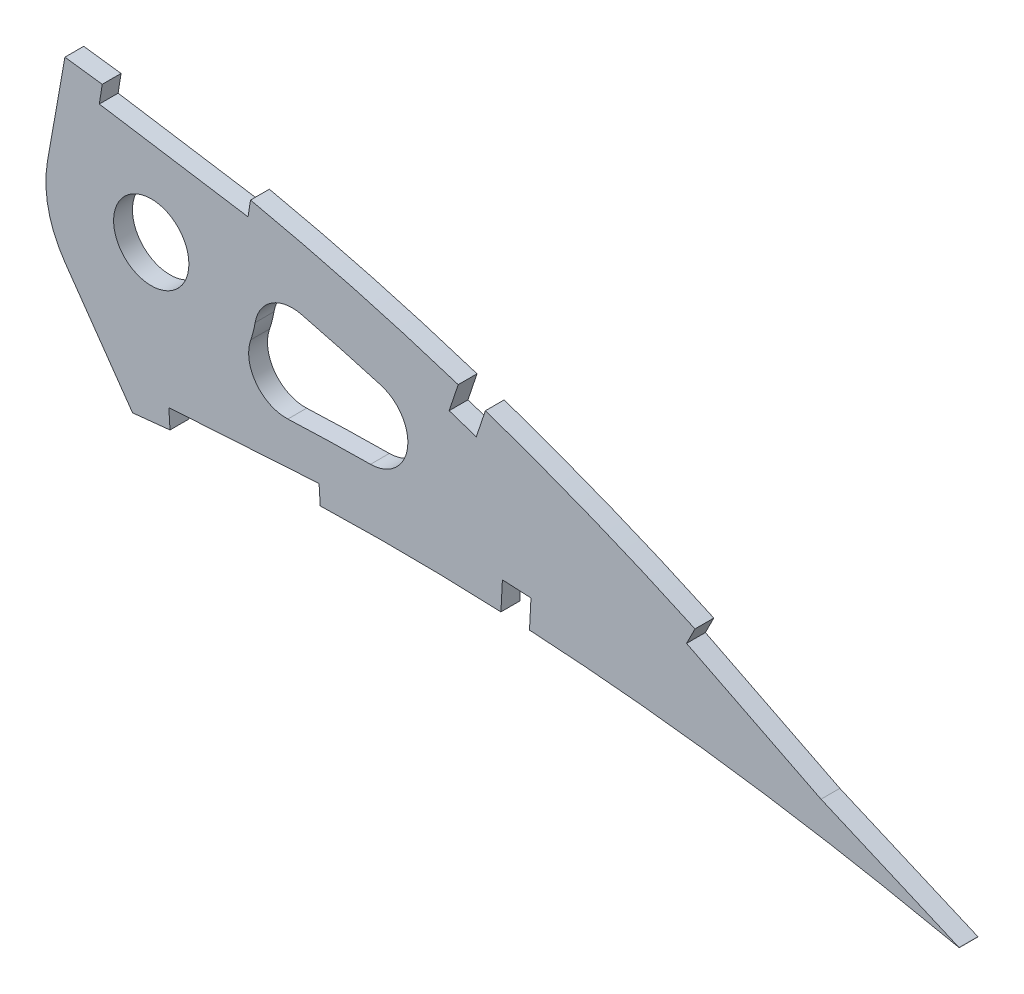
SolidWorks part; units mm, degrees
material "Plywood"
ref_plane "Front Plane" through (0, 0, 0) normal (0, 0, 1) x (1, 0, 0)
ref_plane "Top Plane" through (0, 0, 0) normal (0, 1, 0) x (1, 0, 0)
ref_plane "Right Plane" through (0, 0, 0) normal (1, 0, 0) x (0, 0, -1)
curve "Curve1"
  spline degree 3 poles (0, 0, 0) (0.1249, -0.5894, 0) (0.3751, -1.7709, 0) (1.0551, -3.4717, 0) (1.9543, -5.1067, 0) (3.0917, -6.6716, 0) (4.4597, -8.1658, 0) (6.0551, -9.5909, 0) (7.8766, -10.9463, 0) (9.9217, -12.2312, 0) (12.1874, -13.447, 0) (14.6712, -14.593, 0) (17.3708, -15.6688, 0) (20.2833, -16.6729, 0) (23.4051, -17.607, 0) (26.7332, -18.4687, 0) (30.2639, -19.2592, 0) (33.9938, -19.9766, 0) (37.9188, -20.6214, 0) (42.0348, -21.1935, 0) (46.3376, -21.6931, 0) (50.823, -22.1192, 0) (55.4866, -22.4726, 0) (60.3236, -22.7538, 0) (65.3294, -22.9634, 0) (70.4993, -23.1008, 0) (75.828, -23.1681, 0) (81.3109, -23.1662, 0) (86.9426, -23.0948, 0) (92.7182, -22.9577, 0) (98.6323, -22.754, 0) (104.6794, -22.4863, 0) (110.8541, -22.1572, 0) (117.1509, -21.7679, 0) (123.5642, -21.32, 0) (130.0885, -20.8172, 0) (136.7178, -20.2607, 0) (143.4464, -19.6538, 0) (150.2683, -18.9994, 0) (157.1776, -18.2998, 0) (164.1682, -17.5581, 0) (171.2339, -16.7767, 0) (178.3687, -15.9599, 0) (185.566, -15.1091, 0) (192.8198, -14.2292, 0) (200.1233, -13.3218, 0) (207.4703, -12.3905, 0) (214.8542, -11.4396, 0) (222.2681, -10.469, 0) (229.7058, -9.4856, 0) (237.1601, -8.4887, 0) (244.6246, -7.4833, 0) (252.0922, -6.4726, 0) (259.5558, -5.4569, 0) (267.0088, -4.4404, 0) (274.4442, -3.4259, 0) (281.8548, -2.4135, 0) (289.2339, -1.4081, 0) (296.574, -0.4098, 0) (303.8684, 0.5795, 0) (311.1101, 1.5569, 0) (318.2922, 2.521, 0) (325.4074, 3.4714, 0) (332.4485, 4.4082, 0) (339.3029, 5.3032, 0) (345.9529, 6.204, 0) (352.4207, 6.9424, 0) (358.808, 7.5727, 0) (365.1214, 8.0894, 0) (371.3533, 8.5001, 0) (377.4966, 8.8075, 0) (383.544, 9.0161, 0) (389.4878, 9.132, 0) (395.3205, 9.1582, 0) (401.0343, 9.1029, 0) (406.6218, 8.9708, 0) (412.075, 8.7675, 0) (417.3864, 8.5002, 0) (422.5485, 8.1759, 0) (427.5535, 7.7996, 0) (432.3944, 7.38, 0) (437.0637, 6.9232, 0) (441.5544, 6.4344, 0) (445.8598, 5.924, 0) (449.973, 5.3952, 0) (453.8879, 4.8568, 0) (457.5982, 4.3142, 0) (461.0979, 3.7743, 0) (464.3817, 3.2423, 0) (467.4441, 2.7253, 0) (470.2803, 2.228, 0) (472.8856, 1.7553, 0) (475.2562, 1.3133, 0) (477.3874, 0.904, 0) (479.2765, 0.5343, 0) (480.9199, 0.2058, 0) (482.3151, -0.077, 0) (483.4599, -0.3128, 0) (484.3523, -0.4979, 0) (484.9907, -0.6325, 0) (485.3743, -0.7125, 0) (485.5448, -0.7489, 0) (485.5874, -0.758, 0) knots 0 0 0 0 0.003638 0.007293 0.011028 0.014901 0.018963 0.023258 0.027821 0.032679 0.037853 0.043362 0.049215 0.055422 0.061989 0.068918 0.076211 0.083868 0.091887 0.100266 0.109 0.118085 0.127515 0.137285 0.147388 0.157816 0.168563 0.179619 0.190977 0.202627 0.21456 0.226767 0.239236 0.251959 0.264924 0.27812 0.291536 0.30516 0.318981 0.332985 0.347163 0.361499 0.375981 0.390597 0.405333 0.420175 0.43511 0.450124 0.465203 0.480333 0.495501 0.51069 0.525887 0.541078 0.556247 0.571382 0.586466 0.601485 0.616424 0.631269 0.646007 0.660621 0.675098 0.689423 0.703582 0.716908 0.730009 0.742952 0.755726 0.76832 0.780724 0.792927 0.804916 0.816679 0.828204 0.839475 0.850481 0.861208 0.871639 0.881763 0.891564 0.901027 0.910139 0.918884 0.927249 0.935221 0.942785 0.949928 0.956638 0.962904 0.968712 0.974054 0.978918 0.983297 0.98718 0.990561 0.993433 0.995791 0.99763 0.998946 0.999737 1 1 1 1
curve "Curve2"
  spline degree 3 poles (486.1938, 0.758, 0) (486.1565, 0.781, 0) (486.0077, 0.8729, 0) (485.6723, 1.0786, 0) (485.1139, 1.4213, 0) (484.3321, 1.8984, 0) (483.3276, 2.5088, 0) (482.0999, 3.2482, 0) (480.6498, 4.1141, 0) (478.9775, 5.1026, 0) (477.0833, 6.2089, 0) (474.9678, 7.4286, 0) (472.6313, 8.7548, 0) (470.0748, 10.182, 0) (467.2989, 11.7035, 0) (464.3043, 13.3123, 0) (461.0921, 15.0004, 0) (457.6635, 16.7605, 0) (454.019, 18.5827, 0) (450.1605, 20.4596, 0) (446.0892, 22.3819, 0) (441.8065, 24.3391, 0) (437.3149, 26.3234, 0) (432.6155, 28.3224, 0) (427.7112, 30.3274, 0) (422.6039, 32.3272, 0) (417.2967, 34.3124, 0) (411.7916, 36.2703, 0) (406.0928, 38.1924, 0) (400.203, 40.0661, 0) (394.1264, 41.8812, 0) (387.8666, 43.626, 0) (381.4288, 45.2916, 0) (374.8171, 46.8658, 0) (368.037, 48.3381, 0) (361.0939, 49.6996, 0) (353.9938, 50.9366, 0) (346.7562, 52.0484, 0) (339.4976, 52.9732, 0) (332.2539, 53.8802, 0) (325.021, 54.7322, 0) (317.6998, 55.5482, 0) (310.2971, 56.3235, 0) (302.8205, 57.0556, 0) (295.2774, 57.7415, 0) (287.6757, 58.3791, 0) (280.0227, 58.9648, 0) (272.3266, 59.4977, 0) (264.5949, 59.9731, 0) (256.8359, 60.3907, 0) (249.0573, 60.7475, 0) (241.2675, 61.0411, 0) (233.4745, 61.2698, 0) (225.6865, 61.4312, 0) (217.912, 61.5245, 0) (210.159, 61.547, 0) (202.4359, 61.4984, 0) (194.7508, 61.377, 0) (187.1122, 61.1811, 0) (179.5282, 60.9103, 0) (172.0069, 60.5649, 0) (164.5567, 60.1418, 0) (157.1855, 59.6438, 0) (149.9016, 59.0688, 0) (142.713, 58.4167, 0) (135.6273, 57.6901, 0) (128.6522, 56.887, 0) (121.7954, 56.0099, 0) (115.0642, 55.0603, 0) (108.4663, 54.0378, 0) (102.0087, 52.9453, 0) (95.6983, 51.784, 0) (89.542, 50.5572, 0) (83.5463, 49.2652, 0) (77.7176, 47.912, 0) (72.062, 46.4999, 0) (66.5855, 45.0315, 0) (61.2937, 43.5103, 0) (56.192, 41.9397, 0) (51.2862, 40.3215, 0) (46.5802, 38.6618, 0) (42.0796, 36.9619, 0) (37.788, 35.2268, 0) (33.7103, 33.4591, 0) (29.8497, 31.6641, 0) (26.2104, 29.8437, 0) (22.7951, 28.0033, 0) (19.6072, 26.1454, 0) (16.6497, 24.2737, 0) (13.924, 22.3929, 0) (11.4337, 20.504, 0) (9.1798, 18.612, 0) (7.1636, 16.7197, 0) (5.388, 14.8284, 0) (3.8531, 12.9414, 0) (2.5606, 11.0602, 0) (1.511, 9.1866, 0) (0.7066, 7.3219, 0) (0.1466, 5.4673, 0) (-0.16, 3.6254, 0) (-0.2363, 1.7948, 0) (-0.0786, 0.5974, 0) (0, 0, 0) knots 0 0 0 0 0.000254 0.001015 0.002283 0.004057 0.006331 0.009105 0.012374 0.016134 0.02038 0.025106 0.030306 0.035972 0.0421 0.048678 0.055702 0.06316 0.071046 0.07935 0.088063 0.097176 0.106678 0.116562 0.126814 0.137428 0.148394 0.1597 0.171338 0.183298 0.19557 0.208144 0.221012 0.234162 0.247587 0.261277 0.275223 0.289414 0.303771 0.317689 0.331784 0.34604 0.360444 0.374983 0.38964 0.404403 0.419257 0.434187 0.449177 0.464215 0.479284 0.49437 0.509458 0.524532 0.539579 0.554583 0.56953 0.584403 0.599191 0.613877 0.628447 0.642889 0.657186 0.671326 0.685294 0.699078 0.712665 0.726043 0.739198 0.752118 0.764792 0.777208 0.789356 0.801224 0.812804 0.824083 0.835055 0.84571 0.856038 0.866034 0.875689 0.884998 0.893953 0.902553 0.910789 0.918661 0.926166 0.933303 0.940071 0.946475 0.952518 0.958205 0.963547 0.968557 0.97325 0.977651 0.981787 0.985694 0.989415 0.993001 0.996508 1 1 1 1
sketch "Sketch1" plane through (0, 0, 0) normal (0, 0, 1) x (1, 0, 0)
  line L10 (485.5874, -0.758) -> (490.1477, -1.6846)
  line L24 (486.1938, 0.758) -> (490.1477, -1.6846)
  spline S2 degree 3 poles (-3866.8103, -1018.8258) (79.7559, 75.3438) (-9.1933, 22.1629) (1.0551, -3.4717) (1.9543, -5.1067) (3.0917, -6.6716) (4.4597, -8.1658) (6.0551, -9.5909) (7.8766, -10.9463) (9.9217, -12.2312) (12.1874, -13.447) (14.6712, -14.593) (17.3708, -15.6688) (20.2833, -16.6729) (23.4051, -17.607) (26.7332, -18.4687) (30.2639, -19.2592) (33.9938, -19.9766) (37.9188, -20.6214) (42.0348, -21.1935) (46.3376, -21.6931) (50.823, -22.1192) (55.4866, -22.4726) (60.3236, -22.7538) (65.3294, -22.9634) (70.4993, -23.1008) (75.828, -23.1681) (81.3109, -23.1662) (86.9426, -23.0948) (92.7182, -22.9577) (98.6323, -22.754) (104.6794, -22.4863) (110.8541, -22.1572) (117.1509, -21.7679) (123.5642, -21.32) (130.0885, -20.8172) (136.7178, -20.2607) (143.4464, -19.6538) (150.2683, -18.9994) (157.1776, -18.2998) (164.1682, -17.5581) (171.2339, -16.7767) (178.3687, -15.9599) (185.566, -15.1091) (192.8198, -14.2292) (200.1233, -13.3218) (207.4703, -12.3905) (214.8542, -11.4396) (222.2681, -10.469) (229.7058, -9.4856) (237.1601, -8.4887) (244.6246, -7.4833) (252.0922, -6.4726) (259.5558, -5.4569) (267.0088, -4.4404) (274.4442, -3.4259) (281.8548, -2.4135) (289.2339, -1.4081) (296.574, -0.4098) (303.8684, 0.5795) (311.1101, 1.5569) (318.2922, 2.521) (325.4074, 3.4714) (332.4485, 4.4082) (339.3029, 5.3032) (345.9529, 6.204) (352.4207, 6.9424) (358.808, 7.5727) (365.1214, 8.0894) (371.3533, 8.5001) (377.4966, 8.8075) (383.544, 9.0161) (389.4878, 9.132) (395.3205, 9.1582) (401.0343, 9.1029) (406.6218, 8.9708) (412.075, 8.7675) (417.3864, 8.5002) (422.5485, 8.1759) (427.5535, 7.7996) (432.3944, 7.38) (437.0637, 6.9232) (441.5544, 6.4344) (445.8598, 5.924) (449.973, 5.3952) (453.8879, 4.8568) (457.5982, 4.3142) (461.0979, 3.7743) (464.3817, 3.2423) (467.4441, 2.7253) (470.2803, 2.228) (472.8856, 1.7553) (475.2562, 1.3133) (477.3874, 0.904) (479.2765, 0.5343) (480.9199, 0.2058) (482.3151, -0.077) (483.4599, -0.3128) (484.3523, -0.4979) (484.9907, -0.6325) (504.0158, -4.6034) (520.901, -17.6411) (1368.8084, 3899.3631) knots -0.155184 -0.155184 -0.155184 -0.155184 0.003638 0.007293 0.011028 0.014901 0.018963 0.023258 0.027821 0.032679 0.037853 0.043362 0.049215 0.055422 0.061989 0.068918 0.076211 0.083868 0.091887 0.100266 0.109 0.118085 0.127515 0.137285 0.147388 0.157816 0.168563 0.179619 0.190977 0.202627 0.21456 0.226767 0.239236 0.251959 0.264924 0.27812 0.291536 0.30516 0.318981 0.332985 0.347163 0.361499 0.375981 0.390597 0.405333 0.420175 0.43511 0.450124 0.465203 0.480333 0.495501 0.51069 0.525887 0.541078 0.556247 0.571382 0.586466 0.601485 0.616424 0.631269 0.646007 0.660621 0.675098 0.689423 0.703582 0.716908 0.730009 0.742952 0.755726 0.76832 0.780724 0.792927 0.804916 0.816679 0.828204 0.839475 0.850481 0.861208 0.871639 0.881763 0.891564 0.901027 0.910139 0.918884 0.927249 0.935221 0.942785 0.949928 0.956638 0.962904 0.968712 0.974054 0.978918 0.983297 0.98718 0.990561 0.993433 0.995791 0.99763 0.998946 0.999737 1.115177 1.115177 1.115177 1.115177 only from (0, 0) to (485.5874, -0.758) construction
  spline S3 degree 3 poles (2637.6242, 3371.1949) (518.0891, -28.6046) (504.1645, -10.2642) (485.6723, 1.0786) (485.1139, 1.4213) (484.3321, 1.8984) (483.3276, 2.5088) (482.0999, 3.2482) (480.6498, 4.1141) (478.9775, 5.1026) (477.0833, 6.2089) (474.9678, 7.4286) (472.6313, 8.7548) (470.0748, 10.182) (467.2989, 11.7035) (464.3043, 13.3123) (461.0921, 15.0004) (457.6635, 16.7605) (454.019, 18.5827) (450.1605, 20.4596) (446.0892, 22.3819) (441.8065, 24.3391) (437.3149, 26.3234) (432.6155, 28.3224) (427.7112, 30.3274) (422.6039, 32.3272) (417.2967, 34.3124) (411.7916, 36.2703) (406.0928, 38.1924) (400.203, 40.0661) (394.1264, 41.8812) (387.8666, 43.626) (381.4288, 45.2916) (374.8171, 46.8658) (368.037, 48.3381) (361.0939, 49.6996) (353.9938, 50.9366) (346.7562, 52.0484) (339.4976, 52.9732) (332.2539, 53.8802) (325.021, 54.7322) (317.6998, 55.5482) (310.2971, 56.3235) (302.8205, 57.0556) (295.2774, 57.7415) (287.6757, 58.3791) (280.0227, 58.9648) (272.3266, 59.4977) (264.5949, 59.9731) (256.8359, 60.3907) (249.0573, 60.7475) (241.2675, 61.0411) (233.4745, 61.2698) (225.6865, 61.4312) (217.912, 61.5245) (210.159, 61.547) (202.4359, 61.4984) (194.7508, 61.377) (187.1122, 61.1811) (179.5282, 60.9103) (172.0069, 60.5649) (164.5567, 60.1418) (157.1855, 59.6438) (149.9016, 59.0688) (142.713, 58.4167) (135.6273, 57.6901) (128.6522, 56.887) (121.7954, 56.0099) (115.0642, 55.0603) (108.4663, 54.0378) (102.0087, 52.9453) (95.6983, 51.784) (89.542, 50.5572) (83.5463, 49.2652) (77.7176, 47.912) (72.062, 46.4999) (66.5855, 45.0315) (61.2937, 43.5103) (56.192, 41.9397) (51.2862, 40.3215) (46.5802, 38.6618) (42.0796, 36.9619) (37.788, 35.2268) (33.7103, 33.4591) (29.8497, 31.6641) (26.2104, 29.8437) (22.7951, 28.0033) (19.6072, 26.1454) (16.6497, 24.2737) (13.924, 22.3929) (11.4337, 20.504) (9.1798, 18.612) (7.1636, 16.7197) (5.388, 14.8284) (3.8531, 12.9414) (2.5606, 11.0602) (1.511, 9.1866) (0.7066, 7.3219) (0.1466, 5.4673) (-0.16, 3.6254) (-1.3078, -23.9112) (100.477, -44.4073) (-3985.5392, -325.5751) knots -0.123624 -0.123624 -0.123624 -0.123624 0.000254 0.001015 0.002283 0.004057 0.006331 0.009105 0.012374 0.016134 0.02038 0.025106 0.030306 0.035972 0.0421 0.048678 0.055702 0.06316 0.071046 0.07935 0.088063 0.097176 0.106678 0.116562 0.126814 0.137428 0.148394 0.1597 0.171338 0.183298 0.19557 0.208144 0.221012 0.234162 0.247587 0.261277 0.275223 0.289414 0.303771 0.317689 0.331784 0.34604 0.360444 0.374983 0.38964 0.404403 0.419257 0.434187 0.449177 0.464215 0.479284 0.49437 0.509458 0.524532 0.539579 0.554583 0.56953 0.584403 0.599191 0.613877 0.628447 0.642889 0.657186 0.671326 0.685294 0.699078 0.712665 0.726043 0.739198 0.752118 0.764792 0.777208 0.789356 0.801224 0.812804 0.824083 0.835055 0.84571 0.856038 0.866034 0.875689 0.884998 0.893953 0.902553 0.910789 0.918661 0.926166 0.933303 0.940071 0.946475 0.952518 0.958205 0.963547 0.968557 0.97325 0.977651 0.981787 0.985694 0.989415 0.993001 0.996508 1.148636 1.148636 1.148636 1.148636 only from (486.1938, 0.758) to (0, 0) construction
  spline S4 degree 3 poles (0, 0) (0.1249, -0.5894) (0.3751, -1.7709) (1.0551, -3.4717) (1.9543, -5.1067) (3.0917, -6.6716) (4.4597, -8.1658) (6.0551, -9.5909) (7.8766, -10.9463) (9.9217, -12.2312) (12.1874, -13.447) (14.6712, -14.593) (17.3708, -15.6688) (20.2833, -16.6729) (23.4051, -17.607) (26.7332, -18.4687) (30.2639, -19.2592) (33.9938, -19.9766) (37.9188, -20.6214) (42.0348, -21.1935) (46.3376, -21.6931) (50.823, -22.1192) (55.4866, -22.4726) (60.3236, -22.7538) (65.3294, -22.9634) (70.4993, -23.1008) (75.828, -23.1681) (81.3109, -23.1662) (86.9426, -23.0948) (92.7182, -22.9577) (98.6323, -22.754) (104.6794, -22.4863) (110.8541, -22.1572) (117.1509, -21.7679) (123.5642, -21.32) (130.0885, -20.8172) (136.7178, -20.2607) (143.4464, -19.6538) (150.2683, -18.9994) (157.1776, -18.2998) (164.1682, -17.5581) (171.2339, -16.7767) (178.3687, -15.9599) (185.566, -15.1091) (192.8198, -14.2292) (200.1233, -13.3218) (207.4703, -12.3905) (214.8542, -11.4396) (222.2681, -10.469) (229.7058, -9.4856) (237.1601, -8.4887) (244.6246, -7.4833) (252.0922, -6.4726) (259.5558, -5.4569) (267.0088, -4.4404) (274.4442, -3.4259) (281.8548, -2.4135) (289.2339, -1.4081) (296.574, -0.4098) (303.8684, 0.5795) (311.1101, 1.5569) (318.2922, 2.521) (325.4074, 3.4714) (332.4485, 4.4082) (339.3029, 5.3032) (345.9529, 6.204) (352.4207, 6.9424) (358.808, 7.5727) (365.1214, 8.0894) (371.3533, 8.5001) (377.4966, 8.8075) (383.544, 9.0161) (389.4878, 9.132) (395.3205, 9.1582) (401.0343, 9.1029) (406.6218, 8.9708) (412.075, 8.7675) (417.3864, 8.5002) (422.5485, 8.1759) (427.5535, 7.7996) (432.3944, 7.38) (437.0637, 6.9232) (441.5544, 6.4344) (445.8598, 5.924) (449.973, 5.3952) (453.8879, 4.8568) (457.5982, 4.3142) (461.0979, 3.7743) (464.3817, 3.2423) (467.4441, 2.7253) (470.2803, 2.228) (472.8856, 1.7553) (475.2562, 1.3133) (477.3874, 0.904) (479.2765, 0.5343) (480.9199, 0.2058) (482.3151, -0.077) (483.4599, -0.3128) (484.3523, -0.4979) (484.9907, -0.6325) (485.3743, -0.7125) (485.5448, -0.7489) (485.5874, -0.758) knots 0 0 0 0 0.003638 0.007293 0.011028 0.014901 0.018963 0.023258 0.027821 0.032679 0.037853 0.043362 0.049215 0.055422 0.061989 0.068918 0.076211 0.083868 0.091887 0.100266 0.109 0.118085 0.127515 0.137285 0.147388 0.157816 0.168563 0.179619 0.190977 0.202627 0.21456 0.226767 0.239236 0.251959 0.264924 0.27812 0.291536 0.30516 0.318981 0.332985 0.347163 0.361499 0.375981 0.390597 0.405333 0.420175 0.43511 0.450124 0.465203 0.480333 0.495501 0.51069 0.525887 0.541078 0.556247 0.571382 0.586466 0.601485 0.616424 0.631269 0.646007 0.660621 0.675098 0.689423 0.703582 0.716908 0.730009 0.742952 0.755726 0.76832 0.780724 0.792927 0.804916 0.816679 0.828204 0.839475 0.850481 0.861208 0.871639 0.881763 0.891564 0.901027 0.910139 0.918884 0.927249 0.935221 0.942785 0.949928 0.956638 0.962904 0.968712 0.974054 0.978918 0.983297 0.98718 0.990561 0.993433 0.995791 0.99763 0.998946 0.999737 1 1 1 1
  spline S5 degree 3 poles (486.1938, 0.758) (486.1565, 0.781) (486.0077, 0.8729) (485.6723, 1.0786) (485.1139, 1.4213) (484.3321, 1.8984) (483.3276, 2.5088) (482.0999, 3.2482) (480.6498, 4.1141) (478.9775, 5.1026) (477.0833, 6.2089) (474.9678, 7.4286) (472.6313, 8.7548) (470.0748, 10.182) (467.2989, 11.7035) (464.3043, 13.3123) (461.0921, 15.0004) (457.6635, 16.7605) (454.019, 18.5827) (450.1605, 20.4596) (446.0892, 22.3819) (441.8065, 24.3391) (437.3149, 26.3234) (432.6155, 28.3224) (427.7112, 30.3274) (422.6039, 32.3272) (417.2967, 34.3124) (411.7916, 36.2703) (406.0928, 38.1924) (400.203, 40.0661) (394.1264, 41.8812) (387.8666, 43.626) (381.4288, 45.2916) (374.8171, 46.8658) (368.037, 48.3381) (361.0939, 49.6996) (353.9938, 50.9366) (346.7562, 52.0484) (339.4976, 52.9732) (332.2539, 53.8802) (325.021, 54.7322) (317.6998, 55.5482) (310.2971, 56.3235) (302.8205, 57.0556) (295.2774, 57.7415) (287.6757, 58.3791) (280.0227, 58.9648) (272.3266, 59.4977) (264.5949, 59.9731) (256.8359, 60.3907) (249.0573, 60.7475) (241.2675, 61.0411) (233.4745, 61.2698) (225.6865, 61.4312) (217.912, 61.5245) (210.159, 61.547) (202.4359, 61.4984) (194.7508, 61.377) (187.1122, 61.1811) (179.5282, 60.9103) (172.0069, 60.5649) (164.5567, 60.1418) (157.1855, 59.6438) (149.9016, 59.0688) (142.713, 58.4167) (135.6273, 57.6901) (128.6522, 56.887) (121.7954, 56.0099) (115.0642, 55.0603) (108.4663, 54.0378) (102.0087, 52.9453) (95.6983, 51.784) (89.542, 50.5572) (83.5463, 49.2652) (77.7176, 47.912) (72.062, 46.4999) (66.5855, 45.0315) (61.2937, 43.5103) (56.192, 41.9397) (51.2862, 40.3215) (46.5802, 38.6618) (42.0796, 36.9619) (37.788, 35.2268) (33.7103, 33.4591) (29.8497, 31.6641) (26.2104, 29.8437) (22.7951, 28.0033) (19.6072, 26.1454) (16.6497, 24.2737) (13.924, 22.3929) (11.4337, 20.504) (9.1798, 18.612) (7.1636, 16.7197) (5.388, 14.8284) (3.8531, 12.9414) (2.5606, 11.0602) (1.511, 9.1866) (0.7066, 7.3219) (0.1466, 5.4673) (-0.16, 3.6254) (-0.2363, 1.7948) (-0.0786, 0.5974) (0, 0) knots 0 0 0 0 0.000254 0.001015 0.002283 0.004057 0.006331 0.009105 0.012374 0.016134 0.02038 0.025106 0.030306 0.035972 0.0421 0.048678 0.055702 0.06316 0.071046 0.07935 0.088063 0.097176 0.106678 0.116562 0.126814 0.137428 0.148394 0.1597 0.171338 0.183298 0.19557 0.208144 0.221012 0.234162 0.247587 0.261277 0.275223 0.289414 0.303771 0.317689 0.331784 0.34604 0.360444 0.374983 0.38964 0.404403 0.419257 0.434187 0.449177 0.464215 0.479284 0.49437 0.509458 0.524532 0.539579 0.554583 0.56953 0.584403 0.599191 0.613877 0.628447 0.642889 0.657186 0.671326 0.685294 0.699078 0.712665 0.726043 0.739198 0.752118 0.764792 0.777208 0.789356 0.801224 0.812804 0.824083 0.835055 0.84571 0.856038 0.866034 0.875689 0.884998 0.893953 0.902553 0.910789 0.918661 0.926166 0.933303 0.940071 0.946475 0.952518 0.958205 0.963547 0.968557 0.97325 0.977651 0.981787 0.985694 0.989415 0.993001 0.996508 1 1 1 1
extrude "Boss-Extrude1" add sketch "Sketch1" along normal blind 3.175
sketch "Sketch5" plane through (0, 0, 3.175) normal (0, 0, 1) x (1, 0, 0)
  line L0 (336.323, 36.32) -> (339.2642, 53)
  line L1 (339.2684, 23.0344) -> (350.6801, 6.7368)
  line L2 (353.8329, 33.2326) -> (374.466, 33.2326)
  circle A0 centre (353.8329, 33.2326) radius 6.35
  circle A1 centre (353.8329, 33.2326) radius 6.35
  circle A2 centre (353.8329, 33.2326) radius 17.78
  spline S0 degree 3 poles (-1939.0794, -487.5307) (48.5631, 55.4905) (-7.2206, 17.2286) (1.0551, -3.4717) (1.9543, -5.1067) (3.0917, -6.6716) (4.4597, -8.1658) (6.0551, -9.5909) (7.8766, -10.9463) (9.9217, -12.2312) (12.1874, -13.447) (14.6712, -14.593) (17.3708, -15.6688) (20.2833, -16.6729) (23.4051, -17.607) (26.7332, -18.4687) (30.2639, -19.2592) (33.9938, -19.9766) (37.9188, -20.6214) (42.0348, -21.1935) (46.3376, -21.6931) (50.823, -22.1192) (55.4866, -22.4726) (60.3236, -22.7538) (65.3294, -22.9634) (70.4993, -23.1008) (75.828, -23.1681) (81.3109, -23.1662) (86.9426, -23.0948) (92.7182, -22.9577) (98.6323, -22.754) (104.6794, -22.4863) (110.8541, -22.1572) (117.1509, -21.7679) (123.5642, -21.32) (130.0885, -20.8172) (136.7178, -20.2607) (143.4464, -19.6538) (150.2683, -18.9994) (157.1776, -18.2998) (164.1682, -17.5581) (171.2339, -16.7767) (178.3687, -15.9599) (185.566, -15.1091) (192.8198, -14.2292) (200.1233, -13.3218) (207.4703, -12.3905) (214.8542, -11.4396) (222.2681, -10.469) (229.7058, -9.4856) (237.1601, -8.4887) (244.6246, -7.4833) (252.0922, -6.4726) (259.5558, -5.4569) (267.0088, -4.4404) (274.4442, -3.4259) (281.8548, -2.4135) (289.2339, -1.4081) (296.574, -0.4098) (303.8684, 0.5795) (311.1101, 1.5569) (318.2922, 2.521) (325.4074, 3.4714) (332.4485, 4.4082) (339.3029, 5.3032) (345.9529, 6.204) (352.4207, 6.9424) (358.808, 7.5727) (365.1214, 8.0894) (371.3533, 8.5001) (377.4966, 8.8075) (383.544, 9.0161) (389.4878, 9.132) (395.3205, 9.1582) (401.0343, 9.1029) (406.6218, 8.9708) (412.075, 8.7675) (417.3864, 8.5002) (422.5485, 8.1759) (427.5535, 7.7996) (432.3944, 7.38) (437.0637, 6.9232) (441.5544, 6.4344) (445.8598, 5.924) (449.973, 5.3952) (453.8879, 4.8568) (457.5982, 4.3142) (461.0979, 3.7743) (464.3817, 3.2423) (467.4441, 2.7253) (470.2803, 2.228) (472.8856, 1.7553) (475.2562, 1.3133) (477.3874, 0.904) (479.2765, 0.5343) (480.9199, 0.2058) (482.3151, -0.077) (483.4599, -0.3128) (484.3523, -0.4979) (484.9907, -0.6325) (500.1693, -3.8005) (513.9154, -12.6904) (943.5402, 1945.4943) knots -0.123191 -0.123191 -0.123191 -0.123191 0.003638 0.007293 0.011028 0.014901 0.018963 0.023258 0.027821 0.032679 0.037853 0.043362 0.049215 0.055422 0.061989 0.068918 0.076211 0.083868 0.091887 0.100266 0.109 0.118085 0.127515 0.137285 0.147388 0.157816 0.168563 0.179619 0.190977 0.202627 0.21456 0.226767 0.239236 0.251959 0.264924 0.27812 0.291536 0.30516 0.318981 0.332985 0.347163 0.361499 0.375981 0.390597 0.405333 0.420175 0.43511 0.450124 0.465203 0.480333 0.495501 0.51069 0.525887 0.541078 0.556247 0.571382 0.586466 0.601485 0.616424 0.631269 0.646007 0.660621 0.675098 0.689423 0.703582 0.716908 0.730009 0.742952 0.755726 0.76832 0.780724 0.792927 0.804916 0.816679 0.828204 0.839475 0.850481 0.861208 0.871639 0.881763 0.891564 0.901027 0.910139 0.918884 0.927249 0.935221 0.942785 0.949928 0.956638 0.962904 0.968712 0.974054 0.978918 0.983297 0.98718 0.990561 0.993433 0.995791 0.99763 0.998946 0.999737 1.091411 1.091411 1.091411 1.091411 only from (0, 0) to (485.5874, -0.758) construction
  spline S1 degree 3 poles (1577.8242, 1676.0308) (512.2068, -21.3963) (500.4185, -7.9664) (485.6723, 1.0786) (485.1139, 1.4213) (484.3321, 1.8984) (483.3276, 2.5088) (482.0999, 3.2482) (480.6498, 4.1141) (478.9775, 5.1026) (477.0833, 6.2089) (474.9678, 7.4286) (472.6313, 8.7548) (470.0748, 10.182) (467.2989, 11.7035) (464.3043, 13.3123) (461.0921, 15.0004) (457.6635, 16.7605) (454.019, 18.5827) (450.1605, 20.4596) (446.0892, 22.3819) (441.8065, 24.3391) (437.3149, 26.3234) (432.6155, 28.3224) (427.7112, 30.3274) (422.6039, 32.3272) (417.2967, 34.3124) (411.7916, 36.2703) (406.0928, 38.1924) (400.203, 40.0661) (394.1264, 41.8812) (387.8666, 43.626) (381.4288, 45.2916) (374.8171, 46.8658) (368.037, 48.3381) (361.0939, 49.6996) (353.9938, 50.9366) (346.7562, 52.0484) (339.4976, 52.9732) (332.2539, 53.8802) (325.021, 54.7322) (317.6998, 55.5482) (310.2971, 56.3235) (302.8205, 57.0556) (295.2774, 57.7415) (287.6757, 58.3791) (280.0227, 58.9648) (272.3266, 59.4977) (264.5949, 59.9731) (256.8359, 60.3907) (249.0573, 60.7475) (241.2675, 61.0411) (233.4745, 61.2698) (225.6865, 61.4312) (217.912, 61.5245) (210.159, 61.547) (202.4359, 61.4984) (194.7508, 61.377) (187.1122, 61.1811) (179.5282, 60.9103) (172.0069, 60.5649) (164.5567, 60.1418) (157.1855, 59.6438) (149.9016, 59.0688) (142.713, 58.4167) (135.6273, 57.6901) (128.6522, 56.887) (121.7954, 56.0099) (115.0642, 55.0603) (108.4663, 54.0378) (102.0087, 52.9453) (95.6983, 51.784) (89.542, 50.5572) (83.5463, 49.2652) (77.7176, 47.912) (72.062, 46.4999) (66.5855, 45.0315) (61.2937, 43.5103) (56.192, 41.9397) (51.2862, 40.3215) (46.5802, 38.6618) (42.0796, 36.9619) (37.788, 35.2268) (33.7103, 33.4591) (29.8497, 31.6641) (26.2104, 29.8437) (22.7951, 28.0033) (19.6072, 26.1454) (16.6497, 24.2737) (13.924, 22.3929) (11.4337, 20.504) (9.1798, 18.612) (7.1636, 16.7197) (5.388, 14.8284) (3.8531, 12.9414) (2.5606, 11.0602) (1.511, 9.1866) (0.7066, 7.3219) (0.1466, 5.4673) (-0.16, 3.6254) (-1.0869, -18.6116) (64.385, -36.0874) (-1990.8444, -185.2686) knots -0.098119 -0.098119 -0.098119 -0.098119 0.000254 0.001015 0.002283 0.004057 0.006331 0.009105 0.012374 0.016134 0.02038 0.025106 0.030306 0.035972 0.0421 0.048678 0.055702 0.06316 0.071046 0.07935 0.088063 0.097176 0.106678 0.116562 0.126814 0.137428 0.148394 0.1597 0.171338 0.183298 0.19557 0.208144 0.221012 0.234162 0.247587 0.261277 0.275223 0.289414 0.303771 0.317689 0.331784 0.34604 0.360444 0.374983 0.38964 0.404403 0.419257 0.434187 0.449177 0.464215 0.479284 0.49437 0.509458 0.524532 0.539579 0.554583 0.56953 0.584403 0.599191 0.613877 0.628447 0.642889 0.657186 0.671326 0.685294 0.699078 0.712665 0.726043 0.739198 0.752118 0.764792 0.777208 0.789356 0.801224 0.812804 0.824083 0.835055 0.84571 0.856038 0.866034 0.875689 0.884998 0.893953 0.902553 0.910789 0.918661 0.926166 0.933303 0.940071 0.946475 0.952518 0.958205 0.963547 0.968557 0.97325 0.977651 0.981787 0.985694 0.989415 0.993001 0.996508 1.117993 1.117993 1.117993 1.117993 only from (486.1938, 0.758) to (0, 0) construction
  spline S2 degree 3 poles (0, 0) (0.1249, -0.5894) (0.3751, -1.7709) (1.0551, -3.4717) (1.9543, -5.1067) (3.0917, -6.6716) (4.4597, -8.1658) (6.0551, -9.5909) (7.8766, -10.9463) (9.9217, -12.2312) (12.1874, -13.447) (14.6712, -14.593) (17.3708, -15.6688) (20.2833, -16.6729) (23.4051, -17.607) (26.7332, -18.4687) (30.2639, -19.2592) (33.9938, -19.9766) (37.9188, -20.6214) (42.0348, -21.1935) (46.3376, -21.6931) (50.823, -22.1192) (55.4866, -22.4726) (60.3236, -22.7538) (65.3294, -22.9634) (70.4993, -23.1008) (75.828, -23.1681) (81.3109, -23.1662) (86.9426, -23.0948) (92.7182, -22.9577) (98.6323, -22.754) (104.6794, -22.4863) (110.8541, -22.1572) (117.1509, -21.7679) (123.5642, -21.32) (130.0885, -20.8172) (136.7178, -20.2607) (143.4464, -19.6538) (150.2683, -18.9994) (157.1776, -18.2998) (164.1682, -17.5581) (171.2339, -16.7767) (178.3687, -15.9599) (185.566, -15.1091) (192.8198, -14.2292) (200.1233, -13.3218) (207.4703, -12.3905) (214.8542, -11.4396) (222.2681, -10.469) (229.7058, -9.4856) (237.1601, -8.4887) (244.6246, -7.4833) (252.0922, -6.4726) (259.5558, -5.4569) (267.0088, -4.4404) (274.4442, -3.4259) (281.8548, -2.4135) (289.2339, -1.4081) (296.574, -0.4098) (303.8684, 0.5795) (311.1101, 1.5569) (318.2922, 2.521) (325.4074, 3.4714) (332.4485, 4.4082) (339.3029, 5.3032) (345.9529, 6.204) (352.4207, 6.9424) (358.808, 7.5727) (365.1214, 8.0894) (371.3533, 8.5001) (377.4966, 8.8075) (383.544, 9.0161) (389.4878, 9.132) (395.3205, 9.1582) (401.0343, 9.1029) (406.6218, 8.9708) (412.075, 8.7675) (417.3864, 8.5002) (422.5485, 8.1759) (427.5535, 7.7996) (432.3944, 7.38) (437.0637, 6.9232) (441.5544, 6.4344) (445.8598, 5.924) (449.973, 5.3952) (453.8879, 4.8568) (457.5982, 4.3142) (461.0979, 3.7743) (464.3817, 3.2423) (467.4441, 2.7253) (470.2803, 2.228) (472.8856, 1.7553) (475.2562, 1.3133) (477.3874, 0.904) (479.2765, 0.5343) (480.9199, 0.2058) (482.3151, -0.077) (483.4599, -0.3128) (484.3523, -0.4979) (484.9907, -0.6325) (485.3743, -0.7125) (485.5448, -0.7489) (485.5874, -0.758) knots 0 0 0 0 0.003638 0.007293 0.011028 0.014901 0.018963 0.023258 0.027821 0.032679 0.037853 0.043362 0.049215 0.055422 0.061989 0.068918 0.076211 0.083868 0.091887 0.100266 0.109 0.118085 0.127515 0.137285 0.147388 0.157816 0.168563 0.179619 0.190977 0.202627 0.21456 0.226767 0.239236 0.251959 0.264924 0.27812 0.291536 0.30516 0.318981 0.332985 0.347163 0.361499 0.375981 0.390597 0.405333 0.420175 0.43511 0.450124 0.465203 0.480333 0.495501 0.51069 0.525887 0.541078 0.556247 0.571382 0.586466 0.601485 0.616424 0.631269 0.646007 0.660621 0.675098 0.689423 0.703582 0.716908 0.730009 0.742952 0.755726 0.76832 0.780724 0.792927 0.804916 0.816679 0.828204 0.839475 0.850481 0.861208 0.871639 0.881763 0.891564 0.901027 0.910139 0.918884 0.927249 0.935221 0.942785 0.949928 0.956638 0.962904 0.968712 0.974054 0.978918 0.983297 0.98718 0.990561 0.993433 0.995791 0.99763 0.998946 0.999737 1 1 1 1
  spline S3 degree 3 poles (486.1938, 0.758) (486.1565, 0.781) (486.0077, 0.8729) (485.6723, 1.0786) (485.1139, 1.4213) (484.3321, 1.8984) (483.3276, 2.5088) (482.0999, 3.2482) (480.6498, 4.1141) (478.9775, 5.1026) (477.0833, 6.2089) (474.9678, 7.4286) (472.6313, 8.7548) (470.0748, 10.182) (467.2989, 11.7035) (464.3043, 13.3123) (461.0921, 15.0004) (457.6635, 16.7605) (454.019, 18.5827) (450.1605, 20.4596) (446.0892, 22.3819) (441.8065, 24.3391) (437.3149, 26.3234) (432.6155, 28.3224) (427.7112, 30.3274) (422.6039, 32.3272) (417.2967, 34.3124) (411.7916, 36.2703) (406.0928, 38.1924) (400.203, 40.0661) (394.1264, 41.8812) (387.8666, 43.626) (381.4288, 45.2916) (374.8171, 46.8658) (368.037, 48.3381) (361.0939, 49.6996) (353.9938, 50.9366) (346.7562, 52.0484) (339.4976, 52.9732) (332.2539, 53.8802) (325.021, 54.7322) (317.6998, 55.5482) (310.2971, 56.3235) (302.8205, 57.0556) (295.2774, 57.7415) (287.6757, 58.3791) (280.0227, 58.9648) (272.3266, 59.4977) (264.5949, 59.9731) (256.8359, 60.3907) (249.0573, 60.7475) (241.2675, 61.0411) (233.4745, 61.2698) (225.6865, 61.4312) (217.912, 61.5245) (210.159, 61.547) (202.4359, 61.4984) (194.7508, 61.377) (187.1122, 61.1811) (179.5282, 60.9103) (172.0069, 60.5649) (164.5567, 60.1418) (157.1855, 59.6438) (149.9016, 59.0688) (142.713, 58.4167) (135.6273, 57.6901) (128.6522, 56.887) (121.7954, 56.0099) (115.0642, 55.0603) (108.4663, 54.0378) (102.0087, 52.9453) (95.6983, 51.784) (89.542, 50.5572) (83.5463, 49.2652) (77.7176, 47.912) (72.062, 46.4999) (66.5855, 45.0315) (61.2937, 43.5103) (56.192, 41.9397) (51.2862, 40.3215) (46.5802, 38.6618) (42.0796, 36.9619) (37.788, 35.2268) (33.7103, 33.4591) (29.8497, 31.6641) (26.2104, 29.8437) (22.7951, 28.0033) (19.6072, 26.1454) (16.6497, 24.2737) (13.924, 22.3929) (11.4337, 20.504) (9.1798, 18.612) (7.1636, 16.7197) (5.388, 14.8284) (3.8531, 12.9414) (2.5606, 11.0602) (1.511, 9.1866) (0.7066, 7.3219) (0.1466, 5.4673) (-0.16, 3.6254) (-0.2363, 1.7948) (-0.0786, 0.5974) (0, 0) knots 0 0 0 0 0.000254 0.001015 0.002283 0.004057 0.006331 0.009105 0.012374 0.016134 0.02038 0.025106 0.030306 0.035972 0.0421 0.048678 0.055702 0.06316 0.071046 0.07935 0.088063 0.097176 0.106678 0.116562 0.126814 0.137428 0.148394 0.1597 0.171338 0.183298 0.19557 0.208144 0.221012 0.234162 0.247587 0.261277 0.275223 0.289414 0.303771 0.317689 0.331784 0.34604 0.360444 0.374983 0.38964 0.404403 0.419257 0.434187 0.449177 0.464215 0.479284 0.49437 0.509458 0.524532 0.539579 0.554583 0.56953 0.584403 0.599191 0.613877 0.628447 0.642889 0.657186 0.671326 0.685294 0.699078 0.712665 0.726043 0.739198 0.752118 0.764792 0.777208 0.789356 0.801224 0.812804 0.824083 0.835055 0.84571 0.856038 0.866034 0.875689 0.884998 0.893953 0.902553 0.910789 0.918661 0.926166 0.933303 0.940071 0.946475 0.952518 0.958205 0.963547 0.968557 0.97325 0.977651 0.981787 0.985694 0.989415 0.993001 0.996508 1 1 1 1
  spline S4 degree 1 poles (480.8541, -7.8857) (10.0221, 1.7185) knots 0 0 1 1 construction
  spline S5 degree 1 poles (10.0221, 1.7185) (487.707, 9.1785) knots 0 0 1 1 construction
  spline S6 degree 3 poles (480.8541, -7.8857) (480.7201, -7.8029) (480.4589, -7.6425) (479.8783, -7.2863) (478.9124, -6.6962) (476.9448, -5.5034) (473.0052, -3.1584) (465.0526, 1.417) (448.8811, 10.0668) (425.053, 20.9312) (400.3824, 29.6362) (380.244, 35.2169) (367.5068, 38.1191) (357.2621, 40.0741) (349.5101, 41.3746) (341.8335, 42.449) (333.8166, 43.4475) (325.9049, 44.4061) (315.2983, 45.6009) (296.7451, 47.4959) (270.1814, 49.6136) (238.2719, 51.1465) (206.364, 51.5674) (174.5136, 50.7436) (142.8023, 48.4874) (116.597, 45.208) (95.874, 41.5554) (80.5049, 38.2363) (65.3742, 34.2512) (53.0577, 30.2789) (43.4884, 26.6248) (36.4997, 23.6156) (29.7711, 20.3046) (23.4201, 16.6518) (17.6543, 12.6276) (13.6768, 8.9843) (11.4208, 6.112) (10.5313, 4.5112) (10.1421, 3.4379) (10.0302, 2.9559) (9.9731, 2.5067) (9.9642, 2.3114) (9.9656, 2.2504) (9.9657, 2.2359) (9.9791, 2.0811) (9.9996, 1.9002) (10.0148, 1.7763) (10.0221, 1.7185) knots 0 0 0 0 0.000976 0.001951 0.003903 0.007806 0.015611 0.031223 0.062446 0.124891 0.187337 0.21856 0.249783 0.265394 0.281006 0.296617 0.312229 0.32784 0.343451 0.374674 0.43712 0.499566 0.562011 0.624457 0.686903 0.749348 0.780571 0.811794 0.843017 0.87424 0.889851 0.905463 0.921074 0.936686 0.952297 0.967908 0.975714 0.98352 0.987423 0.991326 0.993277 0.995228 0.996204 0.99718 0.998156 0.998643 0.999131 0.999131 0.999131 0.999131
  spline S7 degree 3 poles (10.0221, 1.7185) (10.034, 1.6636) (10.0599, 1.5462) (10.0999, 1.3723) (10.1389, 1.2199) (10.1476, 1.1921) (10.1628, 1.1452) (10.2268, 0.9816) (10.4203, 0.5862) (10.6781, 0.1667) (11.3398, -0.673) (12.618, -1.867) (15.4809, -3.8036) (20.1586, -5.9835) (26.5914, -8.0226) (33.4675, -9.5952) (40.5985, -10.785) (47.8877, -11.6685) (57.7439, -12.5059) (70.2368, -13.025) (85.3646, -13.0282) (100.5676, -12.5574) (120.8957, -11.433) (146.3656, -9.2898) (176.9642, -5.9687) (207.5889, -2.1743) (238.231, 1.8884) (268.9049, 6.0711) (294.4834, 9.566) (312.4086, 11.9846) (322.6494, 13.3534) (329.0537, 14.2071) (334.1907, 14.8818) (338.0026, 15.3833) (341.8382, 15.8997) (345.8011, 16.4075) (349.7595, 16.8632) (355.0135, 17.4179) (364.2536, 18.2584) (377.4648, 19.063) (398.6452, 19.5221) (425.0949, 18.559) (451.3668, 15.6636) (469.5828, 12.7141) (478.6615, 11.0165) (482.841, 10.1846) (484.7931, 9.786) (485.7414, 9.5904) (486.586, 9.4145) (487.1818, 9.2892) (487.5367, 9.2148) (487.707, 9.1785) knots 0.000905 0.000905 0.000905 0.000905 0.001393 0.00188 0.002856 0.003832 0.004808 0.006759 0.00871 0.012613 0.016516 0.024321 0.032127 0.047737 0.063348 0.078959 0.09457 0.110181 0.125792 0.157013 0.188235 0.219457 0.250679 0.313122 0.375565 0.438009 0.500452 0.562896 0.625339 0.656561 0.672172 0.687783 0.695588 0.703394 0.711199 0.719004 0.72681 0.734615 0.750226 0.781448 0.81267 0.875113 0.937557 0.968778 0.984389 0.992195 0.994146 0.996097 0.998049 0.999024 1 1 1 1
  dimension "D1" = 35.56
  dimension "D2" = 10.16
  dimension "D3" = 80
  dimension "D4" = 55
extrude "Cut-Extrude5" cut sketch "Sketch5" against normal through all contours S7 S6 A2 L0 L1 | S6 S7 L1 A2 | A1 | A2 S7 S6 region at (173.1936, 20.4117, 3.175) region at (347.6625, 33.2326, 3.175) region at (167.5374, 53.746, 3.175) region at (390.6788, 25.1228, 3.175)
sketch "Sketch6" plane through (0, 0, 0) normal (0, 0, -1) x (-1, 0, 0)
  line L0 (-417.6503, 8.4753) -> (-417.6503, 7.6122)
  line L1 (-491.4214, 1.2315) -> (-468.1792, 11.2389)
  line L2 (-417.6503, 7.6122) -> (-412.8307, 7.8598)
  line L3 (-490.1657, -1.6847) -> (-491.4214, 1.2315)
  line L4 (-412.8307, 7.8598) -> (-412.8307, 8.7229)
  line L5 (-468.1792, 11.2389) -> (-445.5766, 22.6173)
  line L6 (-382.3474, 8.9759) -> (-382.3474, 7.8598)
  line L7 (-417.6503, 8.4753) -> (-417.8979, 13.295)
  line L8 (-382.3474, 7.8598) -> (-356.9972, 6.2903)
  line L9 (-417.8979, 13.295) -> (-413.0783, 13.5426)
  line L10 (-356.9972, 6.2903) -> (-356.9972, 7.3864)
  line L11 (-408.6744, 32.2283) -> (-410.2016, 36.8062)
  line L13 (-410.2016, 36.8062) -> (-405.6236, 38.3335)
  line L15 (-382.3474, 8.9759) -> (-382.1488, 12.1446)
  line L17 (-382.1488, 12.1446) -> (-356.7986, 10.5551)
  line L19 (-370.1628, 45.1121) -> (-370.6549, 48.2487)
  line L21 (-370.6549, 48.2487) -> (-345.562, 52.1861)
  line L23 (-466.8364, 8.3603) -> (-490.1657, -1.6847)
  line L25 (-444.149, 19.7814) -> (-466.8364, 8.3603)
  line L27 (-445.5766, 22.6173) -> (-444.149, 19.7814)
  line L31 (-413.0783, 13.5426) -> (-412.8307, 8.7229)
  line L35 (-356.7986, 10.5551) -> (-356.9972, 7.3864)
  line L37 (-404.0964, 33.7555) -> (-408.6744, 32.2283)
  line L39 (-405.6236, 38.3335) -> (-404.0964, 33.7555)
  line L41 (-345.0698, 49.0495) -> (-370.1628, 45.1121)
  line L43 (-345.562, 52.1861) -> (-345.0698, 49.0495)
extrude "Cut-Extrude6" cut sketch "Sketch6" against normal blind 7.62 body kept at (485.5874, -0.758, 0)
fillet "Fillet1" radius 6.35 3 edges at (431.7922, 17.6271, 1.5875) (363.1942, 18.1165, 1.5875) (371.1522, 37.2537, 1.5875)
move or copy body "Body-Move/Copy1" [suppressed] bodies to move or copy 120 parameters "D1"=0, "D2"=0, "D3"=0
